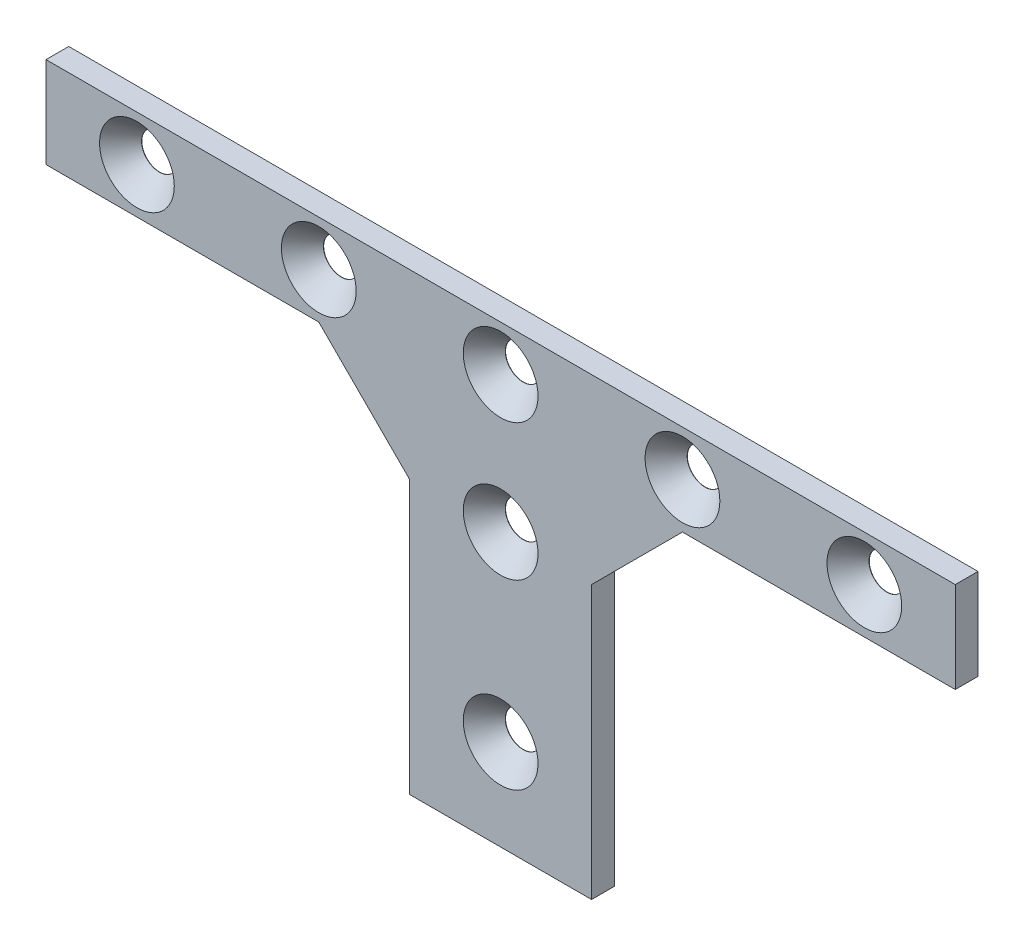
SolidWorks part; units mm, degrees
ref_plane "Front Plane" through (0, 0, 0) normal (0, 0, 1) x (1, 0, 0)
ref_plane "Top Plane" through (0, 0, 0) normal (0, 1, 0) x (1, 0, 0)
ref_plane "Right Plane" through (0, 0, 0) normal (1, 0, 0) x (0, 0, -1)
sketch "Sketch1" plane through (0, 0, 0) normal (0, 0, 1) x (1, 0, 0)
  line L0 (41.275, -25.4) -> (41.275, -63.5)
  line L2 (41.275, -63.5) -> (66.675, -63.5)
  line L4 (66.675, -63.5) -> (66.675, -25.4)
  line L5 (79.375, -12.7) -> (117.475, -12.7)
  line L7 (117.475, -12.7) -> (117.475, 0)
  line L9 (117.475, 0) -> (-9.525, 0)
  line L10 (-9.525, 0) -> (-9.525, -12.7)
  line L11 (-9.525, -12.7) -> (28.575, -12.7)
  line L13 (66.675, -25.4) -> (79.375, -12.7)
  line L14 (53.975, -12.7) -> (53.975, -25.4) construction
  line L15 (41.275, -25.4) -> (28.575, -12.7)
  line L16 (53.975, -63.5) -> (53.975, 0) construction
  line L17 (117.475, -6.35) -> (-9.525, -6.35) construction
  line L18 (117.475, -6.35) -> (104.775, -6.35) construction
  line L19 (104.775, -6.35) -> (79.375, -6.35) construction
  line L20 (79.375, -6.35) -> (53.975, -6.35) construction
  line L21 (53.975, -6.35) -> (28.575, -6.35) construction
  line L22 (28.575, -6.35) -> (3.175, -6.35) construction
  line L23 (53.975, -25.4) -> (53.975, -50.8) construction
  point P10 (0, 0)
  dimension "D3" = 127
extrude "Boss-Extrude1" add sketch "Sketch1" along normal blind 3.175
hole_wizard "#10 Clearance Hole1" positions "Sketch4" profile "Sketch5" hole size "#10" standard "ANSI Inch" end condition through all
sketch "Sketch4" plane through (0, 0, 3.175) normal (0, 0, 1) x (1, 0, 0)
  point P0 (3.175, -6.35)
  point P3 (28.575, -6.35)
  point P6 (53.975, -6.35)
  point P13 (104.775, -6.35)
  point P16 (53.975, -25.4)
  point P19 (53.975, -50.8)
  point P22 (79.375, -6.35)
  point P26 (0, 0)
sketch "Sketch5" plane through (3.175, -6.35, 3.175) normal (1, 0, 0) x (0, -1, 0)
  line L0 (0, 0) -> (0, 3.175)
  line L1 (0, 3.175) -> (2.4892, 3.175)
  line L2 (2.4892, 3.175) -> (2.4892, 3.1411)
  line L3 (2.4892, 3.1411) -> (5.2197, 0)
  line L5 (5.2197, 0) -> (0, 0)
  line L6 (-2.4892, 3.1411) -> (-5.2197, 0) construction
  line L11 (0, -6.35) -> (0, 107.95) construction
  dimension "Thru Hole Dia." = 4.9784
  dimension "Thru Hole Depth" = 3.175
  dimension "Near C'Sink Dia." = 10.4394
  dimension "Near C'Sink Angle" = 82
